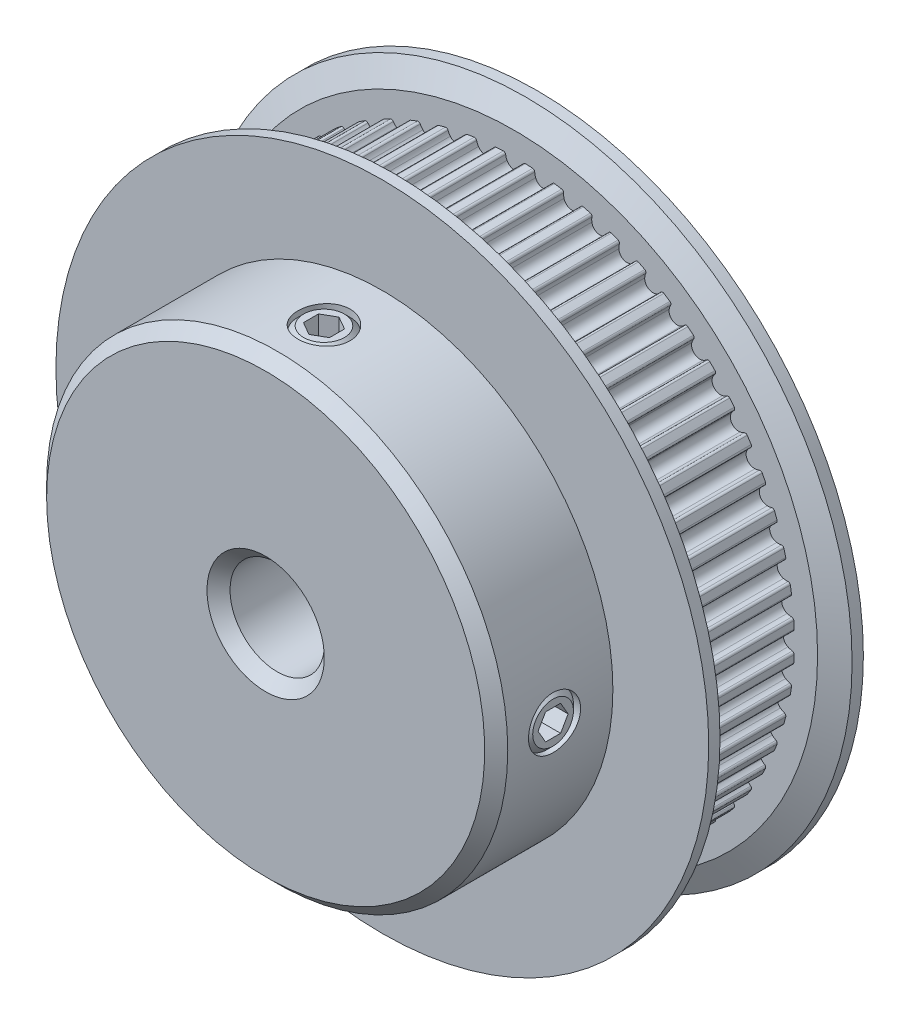
SolidWorks part; units mm, degrees
ref_plane "Front Plane" through (0, 0, 0) normal (0, 0, 1) x (1, 0, 0)
ref_plane "Top Plane" through (0, 0, 0) normal (0, 1, 0) x (1, 0, 0)
ref_plane "Right Plane" through (0, 0, 0) normal (1, 0, 0) x (0, 0, -1)
sketch "Sketch1" plane through (0, 0, 0) normal (0, 0, 1) x (1, 0, 0)
  line L1 (-1.9027, 18.097) -> (1.9027, 18.097) construction
  line L4 (0, 0) -> (0, 18.097) construction
  line L5 (0, 18.097) -> (0, 19.7171) construction
  line L6 (0, 19.101) -> (1.9973, 18.9963) construction
  line L7 (1.9973, 18.9963) -> (2.8966, 18.9017) construction
  line L8 (1.9973, 18.9963) -> (1.9027, 18.097) construction
  line L9 (-1.9973, 18.9963) -> (-1.9027, 18.097) construction
  line L10 (-1.9707, 18.7437) -> (-2.31, 21.971)
  line L11 (-2.31, 21.971) -> (2.31, 21.971)
  line L12 (2.31, 21.971) -> (1.9707, 18.7437)
  circle A0 centre (0, 0) radius 19.101 construction
  circle A1 centre (0, 0) radius 21.971 construction
  circle A2 centre (0, 0) radius 18.847 construction
  arc A3 (-0.4989, 18.4088) -> (0.4989, 18.4088) centre (0, 18.652) ccw
  arc A4 (-0.4989, 18.4088) -> (-0.5897, 18.7039) centre (0.4, 18.847) cw
  arc A5 (-1.9707, 18.7437) -> (-0.7441, 18.8323) centre (0, 0) cw
  arc A6 (-0.5897, 18.7039) -> (-0.7441, 18.8323) centre (-0.7382, 18.6824) ccw
  arc A7 (1.9707, 18.7437) -> (0.7441, 18.8323) centre (0, 0) ccw
  arc A8 (0.5897, 18.7039) -> (0.7441, 18.8323) centre (0.7382, 18.6824) cw
  arc A9 (0.4989, 18.4088) -> (0.5897, 18.7039) centre (-0.4, 18.847) ccw
  point P6 (0, 20.9083)
  point P11 (0, 19.101)
  point P13 (0, 21.971)
  point P14 (0, 18.847)
  dimension "D1" = 1.1913
  dimension "D2" = 0.6161
sketch "Sketch2" plane through (0, 0, 0) normal (1, 0, 0) x (0, 0, -1)
  line L0 (-9.1313, 3.175) -> (9.1313, 3.175)
  line L1 (-9.1313, 3.175) -> (-9.1313, 15.52)
  line L2 (-9.1313, 15.52) -> (-1.2787, 15.52)
  line L3 (-1.2787, 15.52) -> (-1.2787, 21.971)
  line L4 (-1.2787, 21.971) -> (0.2413, 21.971) construction
  line L5 (0.2413, 21.971) -> (0.2413, 18.847) construction
  line L6 (0.2413, 18.847) -> (7.6113, 18.847)
  line L7 (7.6113, 18.847) -> (7.6113, 21.971) construction
  line L8 (7.6113, 21.971) -> (9.1313, 21.971) construction
  line L9 (9.1313, 21.971) -> (9.1313, 3.175)
  line L10 (-9.1313, 0) -> (9.1313, 0) construction
  line L11 (8.3713, 21.971) -> (7.6113, 20.409)
  line L12 (0.2413, 20.409) -> (-0.5187, 21.971)
  line L13 (-1.2787, 21.971) -> (-0.5187, 21.971)
  line L14 (0.2413, 20.409) -> (0.2413, 18.847)
  line L15 (7.6113, 18.847) -> (7.6113, 20.409)
  line L16 (8.3713, 21.971) -> (9.1313, 21.971)
  arc A0 (0.2413, 20.409) -> (-0.5187, 21.971) centre (-1.7439, 20.409) ccw construction
  arc A1 (7.6113, 20.409) -> (8.3713, 21.971) centre (9.5965, 20.409) cw construction
  point P12 (0.2413, 20.409)
  point P14 (-0.5187, 21.971)
  point P20 (7.6113, 20.409)
  point P21 (8.3713, 21.971)
  point P25 (7.6113, 0)
  point P26 (0.2413, 0)
revolve "Revolve1" add sketch "Sketch2" angle 360 mid plane about L10
sketch "Sketch3" plane through (0, 0, 0) normal (0, 0, 1) x (1, 0, 0)
  line L6 (2.31, 21.971) -> (-2.31, 21.971)
  line L7 (1.9707, 18.7437) -> (2.31, 21.971)
  line L8 (-2.31, 21.971) -> (-1.9707, 18.7437)
  line L9 (2.31, 21.971) -> (-2.31, 21.971)
  line L10 (1.9707, 18.7437) -> (2.31, 21.971)
  line L11 (-2.31, 21.971) -> (-1.9707, 18.7437)
  arc A8 (1.9707, 18.7437) -> (0.7441, 18.8323) centre (0, 0) ccw
  arc A9 (0.7441, 18.8323) -> (0.5897, 18.7039) centre (0.7382, 18.6824) ccw
  arc A10 (0.4989, 18.4088) -> (0.5897, 18.7039) centre (-0.4, 18.847) ccw
  arc A11 (-0.4989, 18.4088) -> (0.4989, 18.4088) centre (0, 18.652) ccw
  arc A12 (-0.5897, 18.7039) -> (-0.4989, 18.4088) centre (0.4, 18.847) ccw
  arc A13 (-0.5897, 18.7039) -> (-0.7441, 18.8323) centre (-0.7382, 18.6824) ccw
  arc A14 (-0.7441, 18.8323) -> (-1.9707, 18.7437) centre (0, 0) ccw
  arc A15 (1.9707, 18.7437) -> (0.7441, 18.8323) centre (0, 0) ccw
  arc A16 (0.7441, 18.8323) -> (0.5897, 18.7039) centre (0.7382, 18.6824) ccw
  arc A17 (0.4989, 18.4088) -> (0.5897, 18.7039) centre (-0.4, 18.847) ccw
  arc A18 (-0.4989, 18.4088) -> (0.4989, 18.4088) centre (0, 18.652) ccw
  arc A19 (-0.5897, 18.7039) -> (-0.4989, 18.4088) centre (0.4, 18.847) ccw
  arc A20 (-0.5897, 18.7039) -> (-0.7441, 18.8323) centre (-0.7382, 18.6824) ccw
  arc A21 (-0.7441, 18.8323) -> (-1.9707, 18.7437) centre (0, 0) ccw
  dimension "D1" = 0
extrude "Cut-Extrude1" cut sketch "Sketch3" against normal up to vertex (7.6113 mm away) from vertex up to point (0, 18.847, -7.6113) starting at point (0, 18.847, -0.2413)
pattern_circular "CirPattern1" count 60 over 360 about axis through (0, 0, 9.1313) along (0, 0, 1) of "Cut-Extrude1"
sketch "Sketch4" plane through (0, 0, 0) normal (1, 0, 0) x (0, -1, 0)
  line L0 (0, -1.2787) -> (0, -9.1313) construction
  line L1 (-15.52, -1.2787) -> (15.52, -1.2787) construction
  line L2 (-15.52, -9.1313) -> (15.52, -9.1313) construction
  circle A0 centre (0, -5.205) radius 1.7526
extrude "Cut-Extrude2" cut sketch "Sketch4" along normal through all
ref_plane "Plane1" through (0, 0, 5.205) normal (0, 0, 1) x (1, 0, 0)
sketch "Sketch5" plane through (0, 0, 5.205) normal (0, 0, 1) x (1, 0, 0)
  line L0 (0, 0.1664) -> (0, 15.52) construction
  line L1 (3.175, -1.3716) -> (3.175, 0)
  line L2 (3.556, -1.7526) -> (15.0397, -1.7526)
  line L3 (3.175, 0) -> (15.52, 0) construction
  line L4 (3.175, 0) -> (15.4207, 0)
  line L5 (15.4207, 0) -> (15.4207, -1.3716)
  line L6 (3.556, -1.7526) -> (3.175, -1.3716)
  line L7 (15.4207, -1.3716) -> (15.0397, -1.7526)
  circle A0 centre (0, 0) radius 15.52 construction
  circle A1 centre (0, 0) radius 3.175 construction
  point P2 (3.175, -1.7526)
  point P11 (15.4207, -1.7526)
revolve "Revolve2" add sketch "Sketch5" angle 360 mid plane about L4
sketch "Sketch6" plane through (15.4207, 5.3841, 0) normal (-1, 0, 0) x (0, -1, 0)
  line L1 (5.3841, 6.2169) -> (4.5078, 5.7109)
  line L2 (4.5078, 5.7109) -> (4.5078, 4.6991)
  line L3 (4.5078, 4.6991) -> (5.3841, 4.1931)
  line L4 (5.3841, 4.1931) -> (6.2604, 4.6991)
  line L5 (6.2604, 4.6991) -> (6.2604, 5.7109)
  line L6 (6.2604, 5.7109) -> (5.3841, 6.2169)
  circle A0 centre (5.3841, 5.205) radius 0.8763 construction
  dimension "D1" = 1.7526
extrude "Cut-Extrude3" cut sketch "Sketch6" along normal blind 1.3144
pattern_circular "CirPattern2" count 2 over 90 about axis through (0, 0, 9.1313) along (0, 0, 1) of "Cut-Extrude2", "Revolve2", "Cut-Extrude3"
chamfer "Chamfer1" distance 0.776 angle 45 2 edges at (3.175, 0, 9.1313) (15.52, 0, 9.1313)
ref_axis "Center Axis 1" through (0, 0, -9.1313) along (0, 0, 1)
ref_plane "Contact Plane 1" through (0, 0, 9.1313) normal (0, 0, 1) x (1, 0, 0)
ref_plane "Contact Plane 2" through (0, 0, -9.1313) normal (0, 0, -1) x (-1, 0, 0)
equation "\"D2@Sketch1\" = \"D1@Sketch1\"/2"
equation "\"D1@Sketch6\" = \"Set Screw@Sketch4\" / 2"
equation "\"D1@Cut-Extrude3\" = \"D1@Sketch6\"*.75"
equation "\"D1@Chamfer1\"=\"Hub Dia@Sketch2\"*.025"
